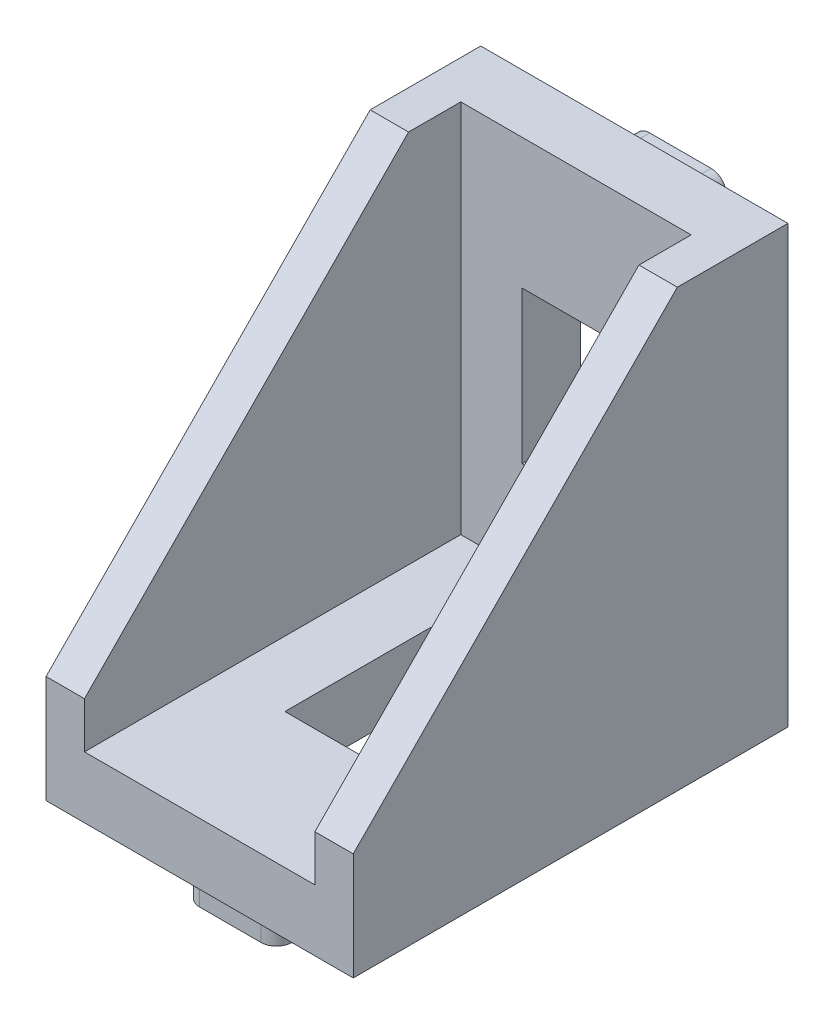
SolidWorks part; units mm, degrees
material "7075-O (SS)"
ref_plane "Front Plane" through (0, 0, 0) normal (0, 0, 1) x (1, 0, 0)
ref_plane "Top Plane" through (0, 0, 0) normal (0, 1, 0) x (1, 0, 0)
ref_plane "Right Plane" through (0, 0, 0) normal (1, 0, 0) x (0, 0, -1)
sketch "Sketch1" plane through (0, 0, 0) normal (0, 0, 1) x (1, 0, 0)
  line L0 (-10, 14.2) -> (10, 14.2)
  line L1 (10, 14.2) -> (10, -14.2)
  line L2 (10, -14.2) -> (-10, -14.2)
  line L3 (-10, -14.2) -> (-10, 14.2)
  dimension "D1" = 20
  dimension "D2" = 28.4
  dimension "D3" = 10
  dimension "D4" = 14.2
extrude "back_wall" add sketch "Sketch1" along normal blind 3.8
sketch "Sketch3" plane through (0, 0, 3.8) normal (0, 0, 1) x (1, 0, 0)
  line L0 (-10, -14.2) -> (-10, -10.2)
  line L1 (-10, 14.2) -> (-10, -14.2) construction
  line L2 (-10, -10.2) -> (10, -10.2)
  line L3 (10, -14.2) -> (10, 14.2) construction
  line L4 (10, -10.2) -> (10, -14.2)
  line L5 (-10, -14.2) -> (10, -14.2) construction
  line L6 (10, -14.2) -> (-10, -14.2)
  dimension "D1" = 4
extrude "bottom_wall" add sketch "Sketch3" along normal blind 24.5
sketch "Sketch4" plane through (-10, 0, 0) normal (-1, 0, 0) x (0, 0, 1)
  line L0 (3.8, 14.2) -> (7.2, 14.2)
  line L1 (28.3, -10.2) -> (3.8, -10.2)
  line L2 (3.8, -10.2) -> (3.8, 14.2)
  line L3 (28.3, -10.2) -> (28.3, -7.2)
  line L4 (28.3, -7.2) -> (7.2, 14.2)
  line L5 (0, 14.2) -> (0, -14.2) construction
  dimension "D1" = 3
  dimension "D2" = 7.2
extrude "left_wall" add sketch "Sketch4" against normal blind 2.5
mirror "right_wall" about plane through (0, 0, 0) normal (1, 0, 0) of "left_wall"
sketch "Sketch6" plane through (0, -10.2, 0) normal (0, 1, 0) x (1, 0, 0)
  line L0 (10, -28.3) -> (10, -7.2) construction
  line L1 (10, 0) -> (-10, 0) construction
  line L2 (-3.25, -19.5) -> (3.25, -19.5)
  line L3 (-3.25, -19.5) -> (-3.25, -10)
  line L4 (-3.25, -10) -> (3.25, -10)
  line L5 (3.25, -19.5) -> (3.25, -10)
  line L7 (-3.25, -19.5) -> (3.25, -10) construction
  line L8 (-3.25, -10) -> (3.25, -19.5) construction
  point P0 (0, -14.75)
  dimension "D1" = 6.5
  dimension "D2" = 9.5
  dimension "D3" = 10
  dimension "D4" = 6.75
extrude "bottom_connection_cutout" cut sketch "Sketch6" against normal blind 11
sketch "Sketch7" plane through (0, 0, 3.8) normal (0, 0, 1) x (1, 0, 0)
  line L0 (7.5, 14.2) -> (-7.5, 14.2) construction
  line L1 (-3.5, -4.2) -> (3.5, -4.2)
  line L2 (-3.5, -4.2) -> (-3.5, 5.7)
  line L3 (-3.5, 5.7) -> (3.5, 5.7)
  line L4 (3.5, -4.2) -> (3.5, 5.7)
  line L5 (-3.5, -4.2) -> (3.5, 5.7) construction
  line L6 (-3.5, 5.7) -> (3.5, -4.2) construction
  line L7 (3.25, -10.2) -> (-3.25, -10.2) construction
  line L9 (-7.5, 14.2) -> (-7.5, -10.2) construction
  line L10 (10, -7.2) -> (10, 14.2) construction
  point P0 (0, 0.75)
  dimension "D1" = 8.5
  dimension "D2" = 6
  dimension "D3" = 6.5
  dimension "D4" = 4
extrude "top_connection_cutout" cut sketch "Sketch7" against normal blind 11
sketch "Sketch8" plane through (0, -14.2, 0) normal (0, -1, 0) x (1, 0, 0)
  line L2 (-3, 26.3) -> (3, 26.3)
  line L3 (-3, 26.3) -> (-3, 24.3)
  line L4 (-3, 24.3) -> (3, 24.3)
  line L5 (3, 26.3) -> (3, 24.3)
  line L6 (-3, 26.3) -> (3, 24.3) construction
  line L7 (-3, 24.3) -> (3, 26.3) construction
  line L9 (-10, 28.3) -> (10, 28.3) construction
  line L11 (-3, 4.3) -> (3, 4.3)
  line L12 (-3, 4.3) -> (-3, 2.3)
  line L13 (-3, 2.3) -> (3, 2.3)
  line L14 (3, 4.3) -> (3, 2.3)
  line L15 (-3, 4.3) -> (3, 2.3) construction
  line L16 (-3, 2.3) -> (3, 4.3) construction
  point P2 (0, 25.3)
  point P7 (0, 3.3)
  dimension "D1" = 4
  dimension "D2" = 2
  dimension "D3" = 6
  dimension "D4" = 24
  dimension "D5" = 2
  dimension "D6" = 6
extrude "bottom_notch" add sketch "Sketch8" along normal blind 3
sketch "Sketch9" plane through (0, 0, 0) normal (0, 0, -1) x (-1, 0, 0)
  line L0 (10, -14.2) -> (-10, -14.2) construction
  line L1 (-3, -10.2) -> (3, -10.2)
  line L2 (-3, -10.2) -> (-3, -12.2)
  line L3 (-3, -12.2) -> (3, -12.2)
  line L4 (3, -10.2) -> (3, -12.2)
  line L5 (-3, -10.2) -> (3, -12.2) construction
  line L6 (-3, -12.2) -> (3, -10.2) construction
  line L7 (-3, 11.8) -> (3, 11.8)
  line L8 (-3, 11.8) -> (-3, 9.8)
  line L9 (-3, 9.8) -> (3, 9.8)
  line L10 (3, 11.8) -> (3, 9.8)
  line L11 (-3, 11.8) -> (3, 9.8) construction
  line L12 (-3, 9.8) -> (3, 11.8) construction
  point P0 (0, -11.2)
  point P5 (0, 10.8)
  dimension "D1" = 4
  dimension "D2" = 2
  dimension "D3" = 2
  dimension "D4" = 24
  dimension "D5" = 6
  dimension "D6" = 6
extrude "top_notch" add sketch "Sketch9" along normal blind 3
fillet "Fillet1" radius 1 16 edges at (3, 9.8, -1.5) (3, 11.8, -1.5) (-3, 11.8, -1.5) (-3, 9.8, -1.5) (-3, -12.2, -1.5) (-3, -10.2, -1.5) (3, -10.2, -1.5) (3, -12.2, -1.5) (3, -15.7, 4.3) (3, -15.7, 2.3) (-3, -15.7, 4.3) (-3, -15.7, 2.3) (-3, -15.7, 26.3) (-3, -15.7, 24.3) (3, -15.7, 26.3) (3, -15.7, 24.3)
sketch "Sketch11" plane through (0, -14.2, 0) normal (0, -1, 0) x (1, 0, 0)
  line L0 (-2, 2.3) -> (2, 2.3) construction
  line L1 (6, 2.3) -> (-6, 2.3)
  line L2 (6, 2.3) -> (6, 8.3)
  line L3 (6, 8.3) -> (-6, 8.3)
  line L4 (-6, 2.3) -> (-6, 8.3)
  line L5 (6, 2.3) -> (-6, 8.3) construction
  line L6 (6, 8.3) -> (-6, 2.3) construction
  line L7 (6, 20.3) -> (-6, 20.3)
  line L8 (6, 20.3) -> (6, 26.3)
  line L9 (6, 26.3) -> (-6, 26.3)
  line L10 (-6, 20.3) -> (-6, 26.3)
  line L11 (6, 20.3) -> (-6, 26.3) construction
  line L12 (6, 26.3) -> (-6, 20.3) construction
  line L14 (2, 26.3) -> (-2, 26.3) construction
  point P0 (0, 5.3)
  point P5 (0, 23.3)
  arc M4 (2, 26.3) -> (3, 25.3) centre (2, 25.3) cw
  arc M5 (3, 25.3) -> (2, 24.3) centre (2, 25.3) cw
  line M6 (2, 24.3) -> (-2, 24.3)
  arc M7 (-2, 24.3) -> (-3, 25.3) centre (-2, 25.3) cw
  arc M8 (-3, 25.3) -> (-2, 26.3) centre (-2, 25.3) cw
  arc M18 (2, 4.3) -> (3, 3.3) centre (2, 3.3) cw
  arc M19 (3, 3.3) -> (2, 2.3) centre (2, 3.3) cw
  arc M21 (-2, 2.3) -> (-3, 3.3) centre (-2, 3.3) cw
  arc M22 (-3, 3.3) -> (-2, 4.3) centre (-2, 3.3) cw
  line M23 (-2, 4.3) -> (2, 4.3)
  dimension "D1" = 12
  dimension "D2" = 6
  dimension "D3" = 6
  dimension "D4" = 12
extrude "bottom_lightening_cutout" cut sketch "Sketch11" against normal blind 3 contours L4 L1 L2 L3 M21 M22 M23 M18 M19 | L10 L7 L8 L9 M4 M5 M6 M7 M8 region at (0, -14.2, 5.6661) region at (0, -14.2, 22.9339)
sketch "Sketch13" plane through (0, 0, 0) normal (0, 0, -1) x (-1, 0, 0)
  line L0 (2, 11.8) -> (-2, 11.8) construction
  line L1 (-6, -6.2) -> (6, -6.2)
  line L2 (-6, -6.2) -> (-6, -12.2)
  line L3 (-6, -12.2) -> (6, -12.2)
  line L4 (6, -6.2) -> (6, -12.2)
  line L5 (-6, -6.2) -> (6, -12.2) construction
  line L6 (-6, -12.2) -> (6, -6.2) construction
  line L7 (-6, 11.8) -> (6, 11.8)
  line L8 (-6, 11.8) -> (-6, 7.8)
  line L9 (-6, 7.8) -> (6, 7.8)
  line L10 (6, 11.8) -> (6, 7.8)
  line L11 (-6, 11.8) -> (6, 7.8) construction
  line L12 (-6, 7.8) -> (6, 11.8) construction
  line L13 (-2, -12.2) -> (2, -12.2) construction
  point P0 (0, -9.2)
  point P5 (0, 9.8)
  line M14 (-2, -10.2) -> (2, -10.2)
  arc M15 (2, -10.2) -> (3, -11.2) centre (2, -11.2) cw
  arc M16 (3, -11.2) -> (2, -12.2) centre (2, -11.2) cw
  arc M18 (-2, -12.2) -> (-3, -11.2) centre (-2, -11.2) cw
  arc M19 (-3, -11.2) -> (-2, -10.2) centre (-2, -11.2) cw
  arc M20 (2, 11.8) -> (3, 10.8) centre (2, 10.8) cw
  arc M21 (3, 10.8) -> (2, 9.8) centre (2, 10.8) cw
  line M22 (2, 9.8) -> (-2, 9.8)
  arc M23 (-2, 9.8) -> (-3, 10.8) centre (-2, 10.8) cw
  arc M24 (-3, 10.8) -> (-2, 11.8) centre (-2, 10.8) cw
  dimension "D1" = 12
  dimension "D2" = 4
  dimension "D3" = 12
  dimension "D4" = 6
extrude "Cut-Extrude2" cut sketch "Sketch13" against normal blind 2 contours L10 L7 L8 L9 M20 M21 M22 M23 M24 | L4 L1 L2 L3 M18 M19 M14 M15 M16 region at (0, -8.8339, 0) region at (0, 9.4977, 0)
